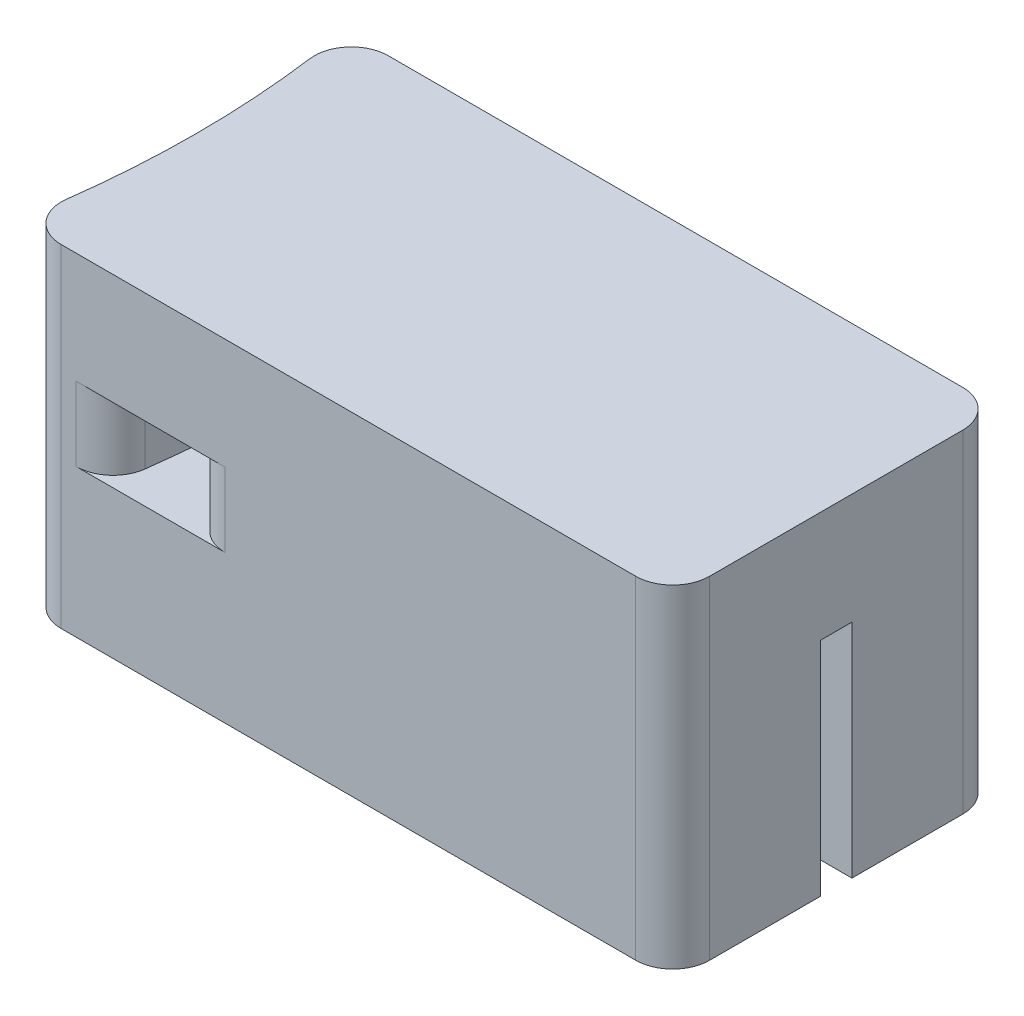
SolidWorks part; units mm, degrees
ref_plane "Front Plane" through (0, 0, 0) normal (0, 0, 1) x (1, 0, 0)
ref_plane "Top Plane" through (0, 0, 0) normal (0, 1, 0) x (1, 0, 0)
ref_plane "Right Plane" through (0, 0, 0) normal (1, 0, 0) x (0, 0, -1)
sketch "Sketch3" plane through (0, 0, 0) normal (0, 1, 0) x (-1, 0, 0)
  line L0 (0, 0.425) -> (0.5196, 0.425)
  line L1 (0.5196, 0.425) -> (2, 0.425) construction
  line L2 (2, 0.425) -> (2.5196, 0.425)
  line L3 (0, 0.425) -> (0, 4.425)
  line L5 (0, 4.425) -> (2.5196, 4.425)
  line L7 (2.5196, 0.425) -> (2.5196, 4.425)
  line L8 (0, 0.425) -> (0, -0.425) construction
  line L10 (0, -0.425) -> (2.5196, -0.425)
  line L11 (0, -0.425) -> (0, -4.425)
  line L12 (0, -4.425) -> (2.5196, -4.425)
  line L13 (2.5196, -0.425) -> (2.5196, -4.425)
  arc A0 (0.5196, 0.425) -> (0.6684, 0.5554) centre (0.5196, 0.575) ccw
  arc A1 (0.6684, 0.5554) -> (0.7609, 0.8632) centre (1.6598, 0.425) cw
  arc A2 (0.7609, 0.8632) -> (1.7587, 0.8632) centre (1.2598, 0.62) cw
  arc A3 (1.7587, 0.8632) -> (1.8513, 0.5554) centre (0.8598, 0.425) cw
  arc A4 (1.8513, 0.5554) -> (2, 0.425) centre (2, 0.575) ccw
  point P12 (0.2598, 0.425)
  dimension "D1" = 0.15
  dimension "D2" = 1
  dimension "D3" = 0.555
  dimension "D4" = 0.4
  dimension "D5" = 0.75
  dimension "D6" = 2
  dimension "D7" = 0.85
  dimension "D8" = 4
extrude "Boss-Extrude2" add sketch "Sketch3" along normal blind 6
pattern_linear "LPattern1" count 5 spacing 2 along (1, 0, 0) of "Boss-Extrude2"
sketch "Sketch4" plane through (0, 6, 0) normal (0, 1, 0) x (1, 0, 0)
  line L5 (-2.5196, 4.425) -> (8, 4.425)
  line L6 (-2.5196, 4.425) -> (-2.5196, -4.425)
  line L7 (-2.5196, -4.425) -> (8, -4.425)
  line L8 (8, 4.425) -> (8, -4.425)
extrude "Boss-Extrude3" add sketch "Sketch4" along normal blind 3
sketch "Sketch8" plane through (0, 9, 0) normal (0, 1, 0) x (1, 0, 0)
  line L0 (-2.5196, 4.425) -> (-9.7144, 4.425)
  line L1 (-2.5196, -4.425) -> (-9.7144, -4.425)
  line L2 (-2.5196, 4.425) -> (-2.5196, -4.425) construction
  line L3 (-2.5196, 4.425) -> (-2.5196, -4.425)
  arc A0 (-5.2546, 4.425) -> (-5.2546, -4.425) centre (-34.3196, 0) cw
  arc A1 (-7.2793, 4.425) -> (-7.2793, -4.425) centre (-34.3196, 0) cw
  arc A2 (-9.7144, 4.425) -> (-9.7144, -4.425) centre (-34.3196, 0) cw
  point P1 (-9.4069, 4.425)
  line M5 (-2.5196, 4.425) -> (-2.5196, -4.425)
  dimension "D1" = 25
  dimension "D3" = 2
  dimension "D4" = 2.4
  dimension "D2" = 2.4
extrude "Boss-Extrude7" add sketch "Sketch8" against normal blind 3 contours L0 A2 L1 L3
extrude "Boss-Extrude8" add sketch "Sketch8<3>" against normal blind 2 from surface contours L0 A2 L1 A1 | L0 A0 L1 M5 region at (-3.7773, 9, 0) region at (-8.2455, 9, 0) starting at face at (1.8182, 6, 0.5198)
sketch "Sketch8<3>" plane through (0, 9, 0) normal (0, 1, 0) x (1, 0, 0) same geometry as "Sketch8"
extrude "Boss-Extrude9" add sketch "Sketch8<4>" against normal up to surface (9 mm away) from surface contours L1 A2 L0 L3 up to face at (2.7402, 0, -2.425) starting at face at (-3.3755, 4, 0)
sketch "Sketch8<4>" plane through (0, 9, 0) normal (0, 1, 0) x (1, 0, 0) same geometry as "Sketch8"
fillet "Fillet1" radius 1 8 edges at (-7.2793, 5, 4.425) (-7.2793, 5, -4.425) (-9.7144, 4.5, 4.425) (-9.7144, 4.5, -4.425) (8, 4.5, 4.425) (8, 4.5, -4.425) (-5.2546, 5, 4.425) (-5.2546, 5, -4.425)
